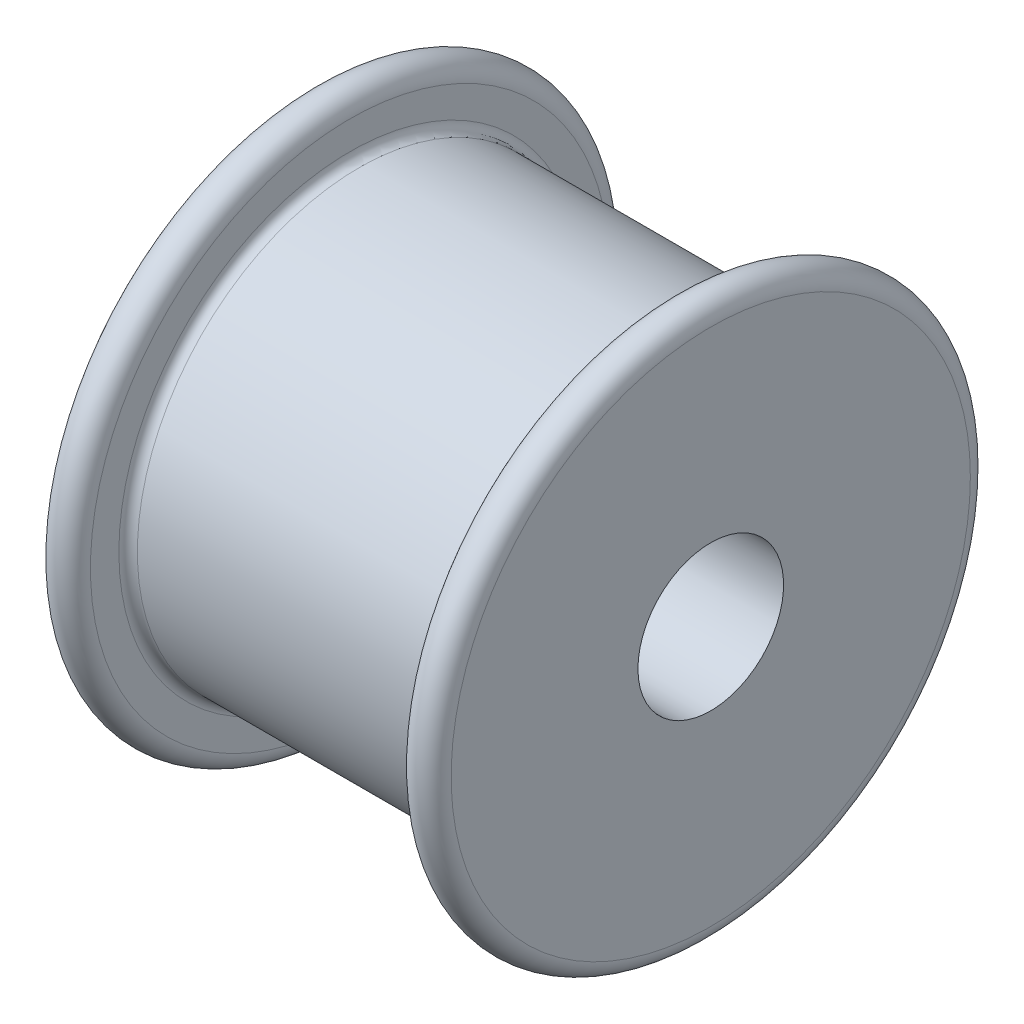
SolidWorks part; units mm, degrees
other "Markup1"
sketch "Sketch4" plane through (-266.7646, 441.8848, 169.5394) normal (-0.1185, 0.1843, 0.9757) x (0.9864, -0.0908, 0.1369)
material "AISI 4130 Steel, annealed at 865C"
ref_plane "Front Plane" through (0, 0, 0) normal (0, 0, 1) x (1, 0, 0)
ref_plane "Top Plane" through (0, 0, 0) normal (0, 1, 0) x (1, 0, 0)
ref_plane "Right Plane" through (0, 0, 0) normal (1, 0, 0) x (0, 0, -1)
other "Center of Mass"
sketch "Sketch1" plane through (0, 0, 0) normal (0, 0, 1) x (1, 0, 0)
  line L0 (-266.6539, 104.9342) -> (717.8936, 104.9342) construction
  line L1 (0, 0) -> (0, 152.4) construction
  line L2 (104.775, 152.4) -> (-104.775, 152.4)
  line L3 (-111.125, 158.75) -> (-111.125, 178.25)
  line L4 (0, 0) -> (-177.3087, 0) construction
  line L5 (-136.525, 178.25) -> (-136.525, 0)
  line L6 (111.125, 158.75) -> (111.125, 178.25)
  line L8 (-136.525, 0) -> (136.525, 0)
  line L9 (136.525, 178.25) -> (136.525, 0)
  arc A0 (-111.125, 158.75) -> (-104.775, 152.4) centre (-104.775, 158.75) ccw
  arc A2 (111.125, 158.75) -> (104.775, 152.4) centre (104.775, 158.75) cw
  arc A4 (-111.125, 178.25) -> (-136.525, 178.25) centre (-123.825, 178.25) ccw
  arc A5 (111.125, 178.25) -> (136.525, 178.25) centre (123.825, 178.25) cw
  point P20 (0, 0)
  dimension "D3" = 6.35
  dimension "D4" = 25.4
  dimension "D6" = 209.55
  dimension "D2" = 152.4
  dimension "D5" = 19.5
revolve "Revolve1" add sketch "Sketch1" angle 360 about L4
sketch "Sketch2" plane through (-136.525, 0, 0) normal (-1, 0, 0) x (0, 0, 1)
  circle A0 centre (0, 0) radius 50
  point P0 (0, 0)
extrude "Cut-Extrude1" cut sketch "Sketch2" against normal through all
ref_axis "Axis1" through (136.525, 0, 0) along (-1, 0, 0)
ref_plane "Plane1" through (0, 0, 0) normal (-1, 0, 0) x (0, 0, 1)
ref_point "Point1"
ref_point "Point2"
sketch "Sketch3" plane through (-136.525, 0, 0) normal (-1, 0, 0) x (0, 0, 1)
  circle A0 centre (0, 0) radius 140
  dimension "D1" = 280
extrude "Cut-Extrude3" cut sketch "Sketch3" against normal blind 215
sketch "Sketch5" plane through (78.475, 0, 0) normal (-1, 0, 0) x (0, 0, 1)
  circle A0 centre (0, 0) radius 50
  circle A1 centre (0, 0) radius 64.5597
extrude "Boss-Extrude1" add sketch "Sketch5" along normal blind 115
